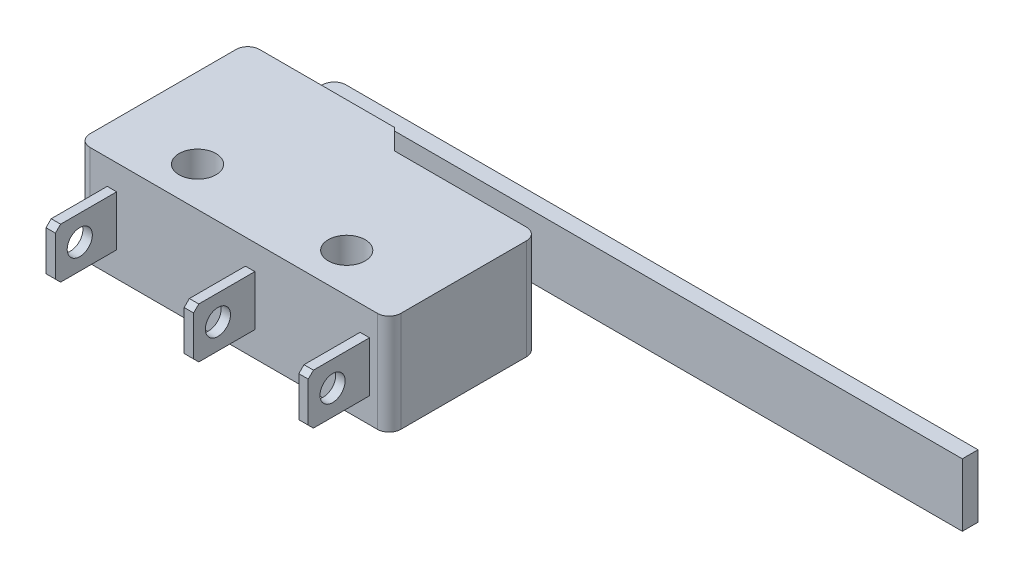
SolidWorks part; units mm, degrees
ref_plane "Front Plane" through (0, 0, 0) normal (0, 0, 1) x (1, 0, 0)
ref_plane "Top Plane" through (0, 0, 0) normal (0, 1, 0) x (1, 0, 0)
ref_plane "Right Plane" through (0, 0, 0) normal (1, 0, 0) x (0, 0, -1)
sketch "Sketch1" plane through (0, 0, 0) normal (0, 1, 0) x (1, 0, 0)
  line L1 (-9.9, 4.75) -> (9.9, 4.75)
  line L2 (-9.9, 4.75) -> (-9.9, -4.75)
  line L3 (-9.9, -4.75) -> (9.9, -4.75)
  line L4 (9.9, 4.75) -> (9.9, -4.75)
  line L5 (-9.9, 4.75) -> (9.9, -4.75) construction
  line L6 (-9.9, -4.75) -> (9.9, 4.75) construction
  point P0 (0, 0)
  dimension "D1" = 19.8
  dimension "D2" = 9.5
extrude "Boss-Extrude1" add sketch "Sketch1" along normal blind 6.4
sketch "Sketch2" plane through (0, 0, -4.75) normal (0, 0, -1) x (-1, 0, 0)
  line L0 (-9.9, 6.4) -> (9.9, 6.4) construction
  line L1 (9.9, 0) -> (-0.75, 0)
  line L2 (9.9, 0) -> (9.9, 6.4)
  line L3 (9.9, 6.4) -> (-0.75, 6.4)
  line L4 (-0.75, 0) -> (-0.75, 6.4)
  dimension "D1" = 10.65
extrude "Boss-Extrude2" add sketch "Sketch2" along normal blind 1.3
chamfer "Chamfer3" distance 1.3 angle 45 1 edges at (0.75, 3.2, -6.05)
fillet "Fillet1" radius 0.75 4 edges at (9.9, 3.2, 4.75) (9.9, 3.2, -4.75) (-9.9, 3.2, 4.75) (-9.9, 3.2, -6.05)
sketch "Sketch3" plane through (0, 0, -6.05) normal (0, 0, -1) x (-1, 0, 0)
  line L0 (9.15, 5.2) -> (0.55, 5.2) construction
  line L1 (9.15, 0) -> (9.15, 6.4) construction
  line L2 (0.55, 6.4) -> (0.55, 0) construction
  line L3 (9.15, 1.2) -> (0.55, 1.2) construction
  line L4 (9.15, 6.4) -> (0.55, 6.4) construction
  line L5 (0.55, 0) -> (9.15, 0) construction
  line L6 (6.4, 1.2) -> (6.4, 5.2) construction
  line L7 (9.9, 6.4) -> (9.9, 0) construction
  line L8 (5.4, 1.2) -> (5.4, 5.2) construction
  line L9 (-9.9, 0) -> (-9.9, 6.4) construction
  line L10 (6.4, 1.2) -> (5.4, 1.2)
  line L11 (6.4, 1.2) -> (6.4, 5.2)
  line L12 (6.4, 5.2) -> (5.4, 5.2)
  line L13 (5.4, 1.2) -> (5.4, 5.2)
  dimension "D1" = 1.2
  dimension "D2" = 1.2
  dimension "D3" = 3.5
  dimension "D4" = 1
extrude "Boss-Extrude3" add sketch "Sketch3" along normal blind 2
sketch "Sketch4" plane through (-5.4, 0, 0) normal (1, 0, 0) x (0, 0, -1)
  line L0 (8.05, 5.2) -> (6.05, 5.2) construction
  line L1 (8.05, 1.2) -> (7.05, 1.2)
  line L2 (8.05, 1.2) -> (8.05, 5.2)
  line L3 (8.05, 5.2) -> (7.05, 5.2)
  line L4 (7.05, 1.2) -> (7.05, 5.2)
  dimension "D1" = 1
extrude "Boss-Extrude4" add sketch "Sketch4" along normal blind 40
fillet "Fillet2" radius 0.75 1 edges at (-6.4, 3.2, -8.05)
sketch "Sketch5" plane through (0, 6.4, 0) normal (0, 1, 0) x (1, 0, 0)
  line L0 (-9.9, 5.3) -> (-9.9, -4) construction
  line L1 (-9.15, -4.75) -> (9.15, -4.75) construction
  circle A0 centre (-4.8, -2.25) radius 1.175
  circle A1 centre (4.7, -2.25) radius 1.175
  dimension "D1" = 2.35
  dimension "D4" = 2.35
  dimension "D2" = 5.1
  dimension "D3" = 2.5
  dimension "D5" = 9.5
extrude "Cut-Extrude1" cut sketch "Sketch5" against normal blind 6.4
sketch "Sketch6" plane through (0, 0, 4.75) normal (0, 0, 1) x (1, 0, 0)
  line L0 (-9.15, 4.8) -> (9.15, 4.8) construction
  line L1 (-9.15, 6.4) -> (-9.15, 0) construction
  line L2 (9.15, 0) -> (9.15, 6.4) construction
  line L3 (-9.15, 6.4) -> (9.15, 6.4) construction
  line L4 (-9.15, 1.6) -> (9.15, 1.6) construction
  line L5 (-9.15, 0) -> (9.15, 0) construction
  line L6 (-9.9, 0) -> (-9.9, 6.4) construction
  line L7 (-8.05, 4.8) -> (-7.45, 4.8)
  line L8 (-8.05, 4.8) -> (-8.05, 1.6)
  line L9 (-8.05, 1.6) -> (-7.45, 1.6)
  line L10 (-7.45, 4.8) -> (-7.45, 1.6)
  line L12 (0.75, 4.8) -> (1.35, 4.8)
  line L13 (0.75, 4.8) -> (0.75, 1.6)
  line L14 (0.75, 1.6) -> (1.35, 1.6)
  line L15 (1.35, 4.8) -> (1.35, 1.6)
  line L16 (8.05, 4.8) -> (8.65, 4.8)
  line L17 (8.05, 4.8) -> (8.05, 1.6)
  line L18 (8.05, 1.6) -> (8.65, 1.6)
  line L19 (8.65, 4.8) -> (8.65, 1.6)
  point P26 (8.05, 3.2)
  dimension "D1" = 1.6
  dimension "D2" = 1.6
  dimension "D3" = 0.6
  dimension "D4" = 1.85
  dimension "D5" = 0.6
  dimension "D6" = 8.8
  dimension "D7" = 0.6
  dimension "D8" = 7.3
extrude "Boss-Extrude5" add sketch "Sketch6" along normal blind 3.9
sketch "Sketch8" plane through (-8.05, 0, 0) normal (-1, 0, 0) x (0, 0, 1)
  line L0 (8.65, 4.8) -> (8.65, 1.6) construction
  circle A0 centre (7.1, 3.2) radius 0.8
  dimension "D1" = 1.6
  dimension "D2" = 1.55
extrude "Cut-Extrude2" cut sketch "Sketch8" against normal blind 16.7
chamfer "Chamfer4" distance 0.33 angle 45 6 edges at (-7.75, 4.8, 8.65) (-7.75, 1.6, 8.65) (8.35, 4.8, 8.65) (8.35, 1.6, 8.65) (1.05, 1.6, 8.65) (1.05, 4.8, 8.65)
